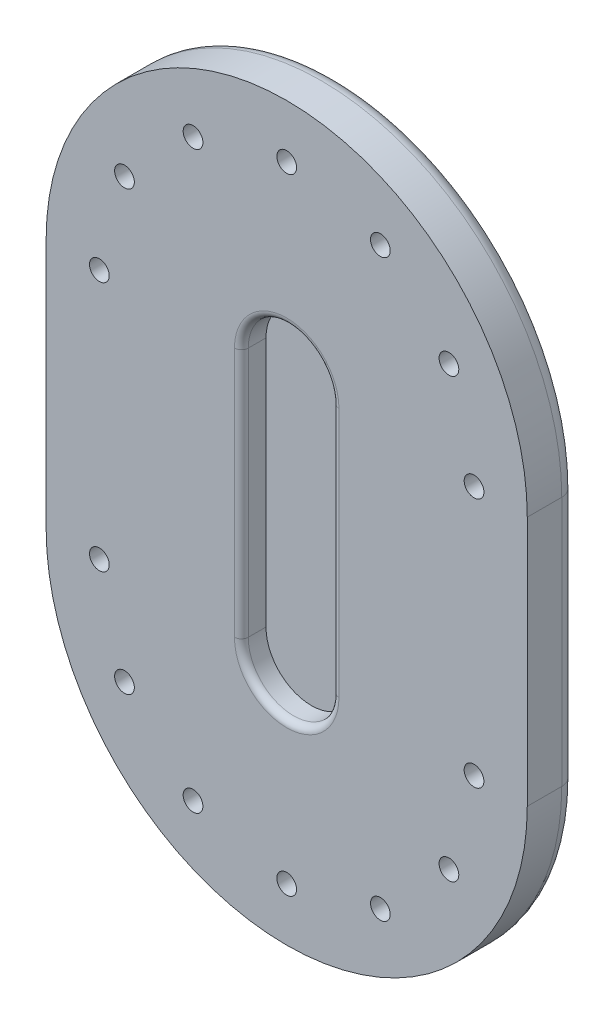
SolidWorks part; units mm, degrees
ref_plane "Front Plane" through (0, 0, 0) normal (0, 0, 1) x (1, 0, 0)
ref_plane "Top Plane" through (0, 0, 0) normal (0, 1, 0) x (1, 0, 0)
ref_plane "Right Plane" through (0, 0, 0) normal (1, 0, 0) x (0, 0, -1)
sketch "Sketch1" plane through (0, 0, 0) normal (0, 0, 1) x (1, 0, 0)
  line L0 (0, -31.75) -> (0, 31.75) construction
  line L1 (-61, -31.75) -> (-61, 31.75)
  line L2 (61, -31.75) -> (61, 31.75)
  line L3 (0, -31.75) -> (0, 31.75) construction
  line L4 (-11.5, -31.75) -> (-11.5, 31.75)
  line L5 (11.5, -31.75) -> (11.5, 31.75)
  arc A0 (-61, -31.75) -> (61, -31.75) centre (0, -31.75) ccw
  arc A1 (61, 31.75) -> (-61, 31.75) centre (0, 31.75) ccw
  arc A2 (-11.5, -31.75) -> (11.5, -31.75) centre (0, -31.75) ccw
  arc A3 (11.5, 31.75) -> (-11.5, 31.75) centre (0, 31.75) ccw
  point P2 (0, 0)
  point P10 (0, 0)
  dimension "D3" = 11.5
  dimension "D1" = 63.5
  dimension "D2" = 122
extrude "Boss-Extrude1" add sketch "Sketch1" against normal blind 12.5 contours A1 L1 A0 L2
extrude "Cut-Extrude1" cut sketch "Sketch1<3>" against normal blind 6.25 contours L5 A3 L4 A2
sketch "Sketch1<3>" plane through (0, 0, 0) normal (0, 0, 1) x (1, 0, 0) same geometry as "Sketch1"
sketch "Sketch4" plane through (0, 0, 0) normal (0, 0, 1) x (1, 0, 0)
  line L0 (-47.5, 31.75) -> (0, 31.75) construction
  point P0 (-47.5, 31.75)
  dimension "D1" = 47.5
sketch "Sketch7" plane through (0, 0, -12.5) normal (0, 0, -1) x (-1, 0, 0)
  point P0 (47.5, 31.75)
hole_wizard "Hole2" positions "Sketch7" profile "Sketch6" legacy
sketch "Sketch6" plane through (-47.5, 31.75, -12.5) normal (1, 0, 0) x (0, 1, 0)
  line L0 (0, 0) -> (0, 100)
  line L1 (0, 100) -> (2.5, 100)
  line L2 (2.5, 100) -> (2.5, 5)
  line L3 (2.5, 5) -> (4.5, 5)
  line L4 (4.5, 5) -> (4.5, 0)
  line L5 (4.5, 0) -> (0, 0)
  line L6 (0, 110) -> (0, -10) construction
  dimension "Diameter" = 5
  dimension "Depth" = 100
  dimension "C-Bore Diameter" = 9
  dimension "C-Bore Depth" = 5
pattern_circular "CirPattern1" count 7 over 180 about axis through (0, 31.75, -12.5) along (0, 0, 1) of "Hole2" reverse direction yes
mirror "Mirror1" about plane through (0, 0, 0) normal (0, 1, 0) of "CirPattern1"
fillet "Fillet1" radius 3.75 4 edges at (61, 0, -12.5) (0, -92.75, -12.5) (-61, 0, -12.5) (0, 92.75, -12.5)
fillet "Fillet2" radius 1.75 4 edges at (0, -43.25, 0) (11.5, 0, 0) (0, 43.25, 0) (-11.5, 0, 0)
